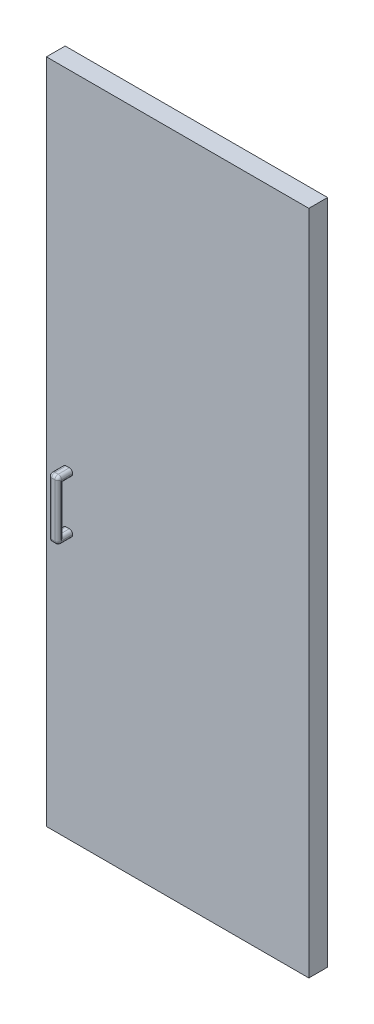
SolidWorks part; units mm, degrees
ref_plane "Front Plane" through (0, 0, 0) normal (0, 0, 1) x (1, 0, 0)
ref_plane "Top Plane" through (0, 0, 0) normal (0, 1, 0) x (1, 0, 0)
ref_plane "Right Plane" through (0, 0, 0) normal (1, 0, 0) x (0, 0, -1)
sketch "Sketch1" plane through (0, 0, 0) normal (0, 0, 1) x (1, 0, 0)
  line L0 (0, 0) -> (0, 18.7953) construction
  line L1 (0, 0) -> (0, 446.2018)
  line L2 (0, 446.2018) -> (-800, 446.2018)
  line L3 (-800, 446.2018) -> (-800, -1585.7982)
  line L4 (-800, -1585.7982) -> (0, -1585.7982)
  line L5 (0, -1585.7982) -> (0, 0)
  line L7 (-203.7641, -553.7982) -> (-173.7641, -553.7982)
  line L8 (-203.7641, -553.7982) -> (-203.7641, -735.7982)
  line L9 (-203.7641, -735.7982) -> (-173.7641, -735.7982)
  line L10 (-173.7641, -553.7982) -> (-173.7641, -735.7982)
  line L11 (-203.7641, -553.7982) -> (-173.7641, -735.7982) construction
  line L12 (-203.7641, -735.7982) -> (-173.7641, -553.7982) construction
  point P9 (-188.7641, -644.7982)
  dimension "D1" = 800
  dimension "D2" = 2032
  dimension "D3" = 30
  dimension "D4" = 182
  dimension "D5" = 850
extrude "Boss-Extrude2" add sketch "Sketch1" along normal blind 57.15 contours L3 L4 L5 L1 L2
sketch "Sketch3" plane through (0, 0, 57.15) normal (0, 0, 1) x (1, 0, 0)
sketch "Sketch4" plane through (0, 0, 57.15) normal (0, 0, 1) x (1, 0, 0)
  line L0 (-750, 0) -> (-750, -526.1226) construction
  line L1 (-800, 446.2018) -> (-800, -1585.7982) construction
  line L2 (-800, -1585.7982) -> (0, -1585.7982) construction
  line L3 (-750, -603.7982) -> (-720, -603.7982)
  line L4 (-750, -603.7982) -> (-750, -785.7982)
  line L5 (-750, -785.7982) -> (-720, -785.7982)
  line L6 (-720, -603.7982) -> (-720, -785.7982)
  point P8 (-735, -785.7982)
  dimension "D1" = 50
  dimension "D2" = 30
  dimension "D3" = 182
  dimension "D4" = 800
extrude "Boss-Extrude3" add sketch "Sketch4" along normal blind 44
sketch "Sketch5" plane through (-750, 0, 0) normal (-1, 0, 0) x (0, 0, 1)
  line L0 (57.15, -624.7982) -> (57.15, -764.7982)
  line L1 (57.15, -603.7982) -> (57.15, -785.7982) construction
  line L2 (57.15, -764.7982) -> (83.15, -764.7982)
  line L3 (83.15, -764.7982) -> (83.15, -624.7982)
  line L4 (83.15, -624.7982) -> (57.15, -624.7982)
  line L5 (101.15, -603.7982) -> (57.15, -603.7982) construction
  dimension "D1" = 21
  dimension "d2" = 140
  dimension "D3" = 26
extrude "Cut-Extrude1" cut sketch "Sketch5" against normal blind 57.15 contours L2 L3 L4 L0
fillet "Fillet1" radius 10 14 edges at (-750, -603.7982, 79.15) (-735, -603.7982, 101.15) (-720, -603.7982, 79.15) (-720, -624.7982, 70.15) (-750, -624.7982, 70.15) (-720, -694.7982, 83.15) (-720, -764.7982, 70.15) (-750, -694.7982, 83.15) (-750, -764.7982, 70.15) (-750, -694.7982, 101.15) (-750, -785.7982, 79.15) (-720, -785.7982, 79.15) (-720, -694.7982, 101.15) (-735, -785.7982, 101.15)
sketch "Sketch6" plane through (0, 0, 0) normal (0, 0, -1) x (-1, 0, 0)
  line L0 (800, 446.2018) -> (800, -1585.7982) construction
  line L1 (655, -924.7982) -> (775, -924.7982)
  line L2 (655, -924.7982) -> (655, -464.7982)
  line L3 (655, -464.7982) -> (775, -464.7982)
  line L4 (775, -924.7982) -> (775, -464.7982)
  line L5 (655, -924.7982) -> (775, -464.7982) construction
  line L6 (655, -464.7982) -> (775, -924.7982) construction
  line L7 (800, -1585.7982) -> (0, -1585.7982) construction
  point P0 (715, -694.7982)
  dimension "D1" = 25
  dimension "D2" = 891
  dimension "D3" = 120
  dimension "D4" = 460
extrude "Boss-Extrude4" add sketch "Sketch6" along normal blind 10
